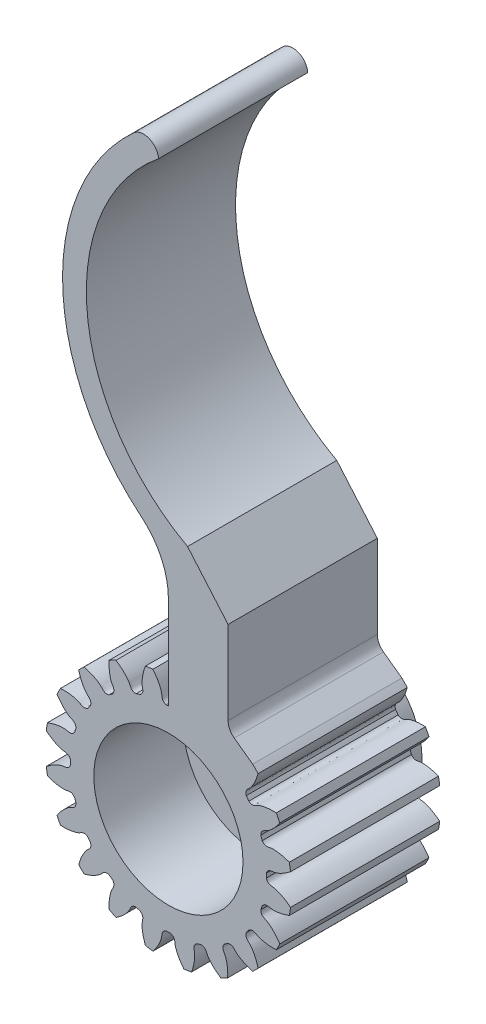
SolidWorks part; units mm, degrees
material "聚脂树脂"
ref_plane "前视基准面" through (0, 0, 0) normal (0, 0, 1) x (1, 0, 0)
ref_plane "上视基准面" through (0, 0, 0) normal (0, 1, 0) x (1, 0, 0)
ref_plane "右视基准面" through (0, 0, 0) normal (1, 0, 0) x (0, 0, -1)
other "Configuration Table"
sketch "草图1" plane through (0, 0, 0) normal (0, 0, 1) x (1, 0, 0)
  circle A0 centre (0, 0) radius 16.5
extrude "凸台-拉伸1" add sketch "草图1" along normal blind 20
ref_axis "基准轴1" through (0, 0, -1.5) along (0, 0, 1)
sketch "草图2" plane through (0, 0, 0) normal (0, 0, 1) x (1, 0, 0)
  line L0 (0, 0) -> (0, 16.5) construction
  circle A0 centre (0, 0) radius 16.5 construction
  arc A1 (0.29, 13.1218) -> (-0.29, 13.1218) centre (0, 0) ccw
  arc A2 (4.7717, 18.7474) -> (-4.7717, 18.7474) centre (0, 0) ccw
  spline S0 degree 3 poles (0.29, 13.1218) (0.9168, 13.3402) (0.8356, 13.7807) (0.9193, 14.205) (0.9283, 14.2463) (0.9395, 14.293) (0.9529, 14.3448) (0.969, 14.4018) (0.9878, 14.4638) (1.0095, 14.5309) (1.0345, 14.6028) (1.0629, 14.6795) (1.0948, 14.7608) (1.1305, 14.8467) (1.1702, 14.9371) (1.2141, 15.0317) (1.2623, 15.1305) (1.315, 15.2334) (1.3725, 15.3401) (1.4349, 15.4506) (1.5023, 15.5646) (1.575, 15.6821) (1.653, 15.8029) (1.7366, 15.9267) (1.826, 16.0534) (1.9211, 16.1829) (2.0223, 16.3149) (2.1296, 16.4493) (2.2432, 16.5859) (2.3632, 16.7244) (2.4897, 16.8646) (2.6229, 17.0065) (2.7628, 17.1496) (2.9095, 17.2939) (3.0632, 17.4391) (3.224, 17.585) (3.3918, 17.7313) (3.567, 17.8779) (3.7493, 18.0245) (3.9391, 18.1709) (4.1363, 18.3167) (4.4122, 18.5125) (4.6259, 18.6545) (4.7717, 18.7474) knots 0 0 0 0 0.165916 0.170906 0.176664 0.183189 0.190482 0.198542 0.207371 0.216967 0.22733 0.238462 0.250361 0.263027 0.276462 0.290664 0.305634 0.321371 0.337876 0.355149 0.37319 0.391998 0.411574 0.431917 0.453028 0.474907 0.497554 0.520968 0.54515 0.570099 0.595817 0.622302 0.649554 0.677575 0.706363 0.735918 0.766242 0.797333 0.829191 0.861818 0.895212 0.929373 1 1 1 1
  spline S1 degree 3 poles (-0.29, 13.1218) (-0.9168, 13.3402) (-0.8356, 13.7807) (-0.9193, 14.205) (-0.9283, 14.2463) (-0.9395, 14.293) (-0.9529, 14.3448) (-0.969, 14.4018) (-0.9878, 14.4638) (-1.0095, 14.5309) (-1.0345, 14.6028) (-1.0629, 14.6795) (-1.0948, 14.7608) (-1.1305, 14.8467) (-1.1702, 14.9371) (-1.2141, 15.0317) (-1.2623, 15.1305) (-1.315, 15.2334) (-1.3725, 15.3401) (-1.4349, 15.4506) (-1.5023, 15.5646) (-1.575, 15.6821) (-1.653, 15.8029) (-1.7366, 15.9267) (-1.826, 16.0534) (-1.9211, 16.1829) (-2.0223, 16.3149) (-2.1296, 16.4493) (-2.2432, 16.5859) (-2.3632, 16.7244) (-2.4897, 16.8646) (-2.6229, 17.0065) (-2.7628, 17.1496) (-2.9095, 17.2939) (-3.0632, 17.4391) (-3.224, 17.585) (-3.3918, 17.7313) (-3.567, 17.8779) (-3.7493, 18.0245) (-3.9391, 18.1709) (-4.1363, 18.3167) (-4.4122, 18.5125) (-4.6259, 18.6545) (-4.7717, 18.7474) knots 0 0 0 0 0.165916 0.170906 0.176664 0.183189 0.190482 0.198542 0.207371 0.216967 0.22733 0.238462 0.250361 0.263027 0.276462 0.290664 0.305634 0.321371 0.337876 0.355149 0.37319 0.391998 0.411574 0.431917 0.453028 0.474907 0.497554 0.520968 0.54515 0.570099 0.595817 0.622302 0.649554 0.677575 0.706363 0.735918 0.766242 0.797333 0.829191 0.861818 0.895212 0.929373 1 1 1 1
extrude "切除-拉伸1" cut sketch "草图2" along normal through all
pattern_circular "阵列(圆周)1" count 20 over 360 about axis through (0, 0, -1.5) along (0, 0, 1) of "切除-拉伸1"
sketch "草图3" plane through (0, 0, 0) normal (0, 0, 1) x (1, 0, 0)
  circle A0 centre (0, 0) radius 15 construction
  dimension "Dn" = 30
sketch "草图4" plane through (0, 0, 0) normal (0, 0, -1) x (-1, 0, 0)
  line L0 (0, 0) -> (67.6919, 0) construction
  line L1 (0, 13.125) -> (0, 76.7697) construction
  line L2 (-15, 0) -> (-15, 67.6903) construction
  line L6 (-7.9502, 14.4584) -> (-11.294, 12.029)
  line L7 (-8, 0) -> (-8, 30.72)
  line L8 (0, 30.72) -> (0, 0)
  line L9 (1.261, 80) -> (1.32, 76)
  line L10 (-8, 0) -> (0, 0)
  circle A2 centre (-15, 55.76) radius 26 construction
  arc A4 (-8, 30.72) -> (1.32, 76) centre (-15, 55.76) ccw
  arc A6 (0.29, 13.1218) -> (-0.29, 13.1218) centre (0, 0) ccw construction
  arc A7 (-2.0665, 16.3701) -> (-3.0932, 16.2075) centre (0, 0) ccw construction
  arc A8 (-3.7791, 12.5692) -> (-4.3306, 12.39) centre (0, 0) ccw construction
  arc A9 (-7.024, 14.9303) -> (-7.9502, 14.4584) centre (0, 0) ccw construction
  arc A10 (0, 13.125) -> (-0.29, 13.1218) centre (0, 0) ccw
  arc A11 (-2.0665, 16.3701) -> (-3.0932, 16.2075) centre (0, 0) ccw
  arc A12 (-3.7791, 12.5692) -> (-4.3306, 12.39) centre (0, 0) ccw
  arc A13 (-7.024, 14.9303) -> (-7.9502, 14.4584) centre (0, 0) ccw
  arc A14 (-7.4782, 10.7862) -> (-7.9474, 10.4453) centre (0, 0) ccw construction
  arc A15 (-7.4782, 10.7862) -> (-7.9474, 10.4453) centre (0, 0) ccw
  circle A16 centre (0, 0) radius 12.5
  circle A17 centre (-15, 55.76) radius 29.189 construction
  arc A18 (0, 30.72) -> (1.261, 80) centre (-15, 55.76) ccw
  spline S2 degree 3 poles (9636.1577, 2672.394) (-75.3968, -18.2301) (0.8601, 5.1856) (-0.9224, 14.2207) (-0.9359, 14.2793) (-0.9529, 14.3448) (-0.969, 14.4018) (-0.9951, 14.4881) (-1.0357, 14.6084) (-1.0961, 14.7664) (-1.1716, 14.9426) (-1.2638, 15.1361) (-1.3741, 15.3456) (-1.5041, 15.5702) (-1.6549, 15.8084) (-1.7965, 16.0133) (-1.9211, 16.1829) (-29.6649, 52.3852) (-347.1976, -138.1957) (9963.7292, 828.2221) knots -3.578314 -3.578314 -3.578314 -3.578314 0.165916 0.170906 0.183189 0.190482 0.198542 0.207371 0.22733 0.250361 0.276462 0.305634 0.337876 0.37319 0.411574 0.453028 0.474907 0.497554 19.082782 19.082782 19.082782 19.082782 only from (-0.29, 13.1218) to (-2.0665, 16.3701) construction
  spline S3 degree 3 poles (-9990.3457, -436.1387) (77.34, 5.961) (-2.4205, 4.666) (-3.5171, 13.8097) (-3.5224, 13.8696) (-3.5265, 13.9372) (-3.5289, 13.9963) (-3.5307, 14.0865) (-3.5293, 14.2134) (-3.5206, 14.3824) (-3.5033, 14.5733) (-3.4754, 14.7858) (-3.4352, 15.0192) (-3.381, 15.2729) (-3.3111, 15.5461) (-3.2398, 15.7847) (-3.1737, 15.9845) (12.0251, 58.9882) (372.9094, -24.1419) (-9732.0043, -2291.2756) knots -3.085746 -3.085746 -3.085746 -3.085746 0.658484 0.663474 0.675757 0.68305 0.691111 0.699939 0.719899 0.742929 0.76903 0.798202 0.830445 0.865758 0.904142 0.945597 0.967475 0.990122 19.575351 19.575351 19.575351 19.575351 only from (-3.7791, 12.5692) to (-3.0932, 16.2075) construction
  spline S4 degree 3 poles (8338.7154, 5519.3342) (-66.0732, -40.6368) (-0.7844, 5.1976) (-5.2717, 13.2396) (-5.3027, 13.2912) (-5.3391, 13.3482) (-5.3719, 13.3975) (-5.4235, 13.4715) (-5.4992, 13.5733) (-5.6055, 13.705) (-5.7318, 13.8492) (-5.8792, 14.0047) (-6.0489, 14.1699) (-6.2419, 14.3433) (-6.459, 14.5233) (-6.6569, 14.6744) (-6.8279, 14.7972) (-44.4009, 40.6543) (-287.4997, -238.7219) (9220.1348, 3866.6477) knots -3.578314 -3.578314 -3.578314 -3.578314 0.165916 0.170906 0.183189 0.190482 0.198542 0.207371 0.22733 0.250361 0.276462 0.305634 0.337876 0.37319 0.411574 0.453028 0.474907 0.497554 19.082782 19.082782 19.082782 19.082782 only from (-4.3306, 12.39) to (-7.024, 14.9303) construction
  spline S5 degree 3 poles (-0.29, 13.1218) (-0.9168, 13.3402) (-0.8356, 13.7807) (-0.9224, 14.2207) (-0.9359, 14.2793) (-0.9529, 14.3448) (-0.969, 14.4018) (-0.9951, 14.4881) (-1.0357, 14.6084) (-1.0961, 14.7664) (-1.1716, 14.9426) (-1.2638, 15.1361) (-1.3741, 15.3456) (-1.5041, 15.5702) (-1.6549, 15.8084) (-1.828, 16.0589) (-1.969, 16.2466) (-2.0515, 16.3512) (-2.0665, 16.3701) knots 0 0 0 0 0.165916 0.170906 0.183189 0.190482 0.198542 0.207371 0.22733 0.250361 0.276462 0.305634 0.337876 0.37319 0.411574 0.453028 0.497554 0.507432 0.507432 0.507432 0.507432
  spline S6 degree 3 poles (-3.7791, 12.5692) (-3.2504, 12.9706) (-3.4637, 13.3644) (-3.5171, 13.8097) (-3.5224, 13.8696) (-3.5265, 13.9372) (-3.5289, 13.9963) (-3.5307, 14.0865) (-3.5293, 14.2134) (-3.5206, 14.3824) (-3.5033, 14.5733) (-3.4754, 14.7858) (-3.4352, 15.0192) (-3.381, 15.2729) (-3.3111, 15.5461) (-3.224, 15.8378) (-3.1479, 16.0599) (-3.1017, 16.1848) (-3.0932, 16.2075) knots 0.492568 0.492568 0.492568 0.492568 0.658484 0.663474 0.675757 0.68305 0.691111 0.699939 0.719899 0.742929 0.76903 0.798202 0.830445 0.865758 0.904142 0.945597 0.990122 1 1 1 1
  spline S7 degree 3 poles (-4.3306, 12.39) (-4.9943, 12.404) (-5.0532, 12.848) (-5.2717, 13.2396) (-5.3027, 13.2912) (-5.3391, 13.3482) (-5.3719, 13.3975) (-5.4235, 13.4715) (-5.4992, 13.5733) (-5.6055, 13.705) (-5.7318, 13.8492) (-5.8792, 14.0047) (-6.0489, 14.1699) (-6.2419, 14.3433) (-6.459, 14.5233) (-6.701, 14.7081) (-6.8931, 14.843) (-7.0039, 14.9169) (-7.024, 14.9303) knots 0 0 0 0 0.165916 0.170906 0.183189 0.190482 0.198542 0.207371 0.22733 0.250361 0.276462 0.305634 0.337876 0.37319 0.411574 0.453028 0.497554 0.507432 0.507432 0.507432 0.507432
  spline S8 degree 3 poles (-9366.6091, -3501.9792) (71.7127, 29.5686) (-3.7439, 3.6897) (-7.6124, 12.047) (-7.636, 12.1023) (-7.6607, 12.1653) (-7.6812, 12.2208) (-7.7108, 12.3061) (-7.7487, 12.4272) (-7.7927, 12.5905) (-7.8352, 12.7775) (-7.8743, 12.9882) (-7.9082, 13.2226) (-7.9351, 13.4806) (-7.9531, 13.762) (-7.959, 14.011) (-7.9578, 14.2215) (-6.7918, 59.817) (362.1182, 92.275) (-8547.643, -5186.4873) knots -3.085746 -3.085746 -3.085746 -3.085746 0.658484 0.663474 0.675757 0.68305 0.691111 0.699939 0.719899 0.742929 0.76903 0.798202 0.830445 0.865758 0.904142 0.945597 0.967475 0.990122 19.575351 19.575351 19.575351 19.575351 only from (-7.4782, 10.7862) to (-7.9502, 14.4584) construction
  spline S9 degree 3 poles (6225.0215, 7826.0035) (-50.2819, -59.0656) (-2.3522, 4.7008) (-9.105, 10.9626) (-9.1503, 11.0021) (-9.2026, 11.0451) (-9.2491, 11.0817) (-9.321, 11.1362) (-9.4245, 11.2097) (-9.5662, 11.302) (-9.7309, 11.4002) (-9.9192, 11.5025) (-10.1316, 11.6072) (-10.3687, 11.7125) (-10.6308, 11.8165) (-10.8658, 11.8991) (-11.0663, 11.963) (-54.7906, 24.9439) (-199.6594, -315.8803) (7574.0095, 6526.5788) knots -3.578314 -3.578314 -3.578314 -3.578314 0.165916 0.170906 0.183189 0.190482 0.198542 0.207371 0.22733 0.250361 0.276462 0.305634 0.337876 0.37319 0.411574 0.453028 0.474907 0.497554 19.082782 19.082782 19.082782 19.082782 only from (-7.9474, 10.4453) to (-11.294, 12.029) construction
  spline S10 degree 3 poles (-7.4782, 10.7862) (-7.0995, 11.3313) (-7.424, 11.64) (-7.6124, 12.047) (-7.636, 12.1023) (-7.6607, 12.1653) (-7.6812, 12.2208) (-7.7108, 12.3061) (-7.7487, 12.4272) (-7.7927, 12.5905) (-7.8352, 12.7775) (-7.8743, 12.9882) (-7.9082, 13.2226) (-7.9351, 13.4806) (-7.9531, 13.762) (-7.9603, 14.0664) (-7.9566, 14.3011) (-7.9513, 14.4342) (-7.9502, 14.4584) knots 0.492568 0.492568 0.492568 0.492568 0.658484 0.663474 0.675757 0.68305 0.691111 0.699939 0.719899 0.742929 0.76903 0.798202 0.830445 0.865758 0.904142 0.945597 0.990122 1 1 1 1
  spline S11 degree 3 poles (-7.9474, 10.4453) (-8.5829, 10.2536) (-8.7761, 10.6576) (-9.105, 10.9626) (-9.1503, 11.0021) (-9.2026, 11.0451) (-9.2491, 11.0817) (-9.321, 11.1362) (-9.4245, 11.2097) (-9.5662, 11.302) (-9.7309, 11.4002) (-9.9192, 11.5025) (-10.1316, 11.6072) (-10.3687, 11.7125) (-10.6308, 11.8165) (-10.9181, 11.9175) (-11.1425, 11.9864) (-11.2707, 12.0225) (-11.294, 12.029) knots 0 0 0 0 0.165916 0.170906 0.183189 0.190482 0.198542 0.207371 0.22733 0.250361 0.276462 0.305634 0.337876 0.37319 0.411574 0.453028 0.497554 0.507432 0.507432 0.507432 0.507432
  dimension "D4" = 52
  dimension "D5" = 80
  dimension "D3" = 25
  dimension "D1" = 15
  dimension "D2" = 30.72
  dimension "D6" = 76
  dimension "D8" = 8
  dimension "D9" = 30.72
extrude "凸台-拉伸2" add sketch "草图4" against normal blind 20 contours S7 A12 S6 A11 S5 A10 L8 A18 L9 A4 L7 L6 A13 | S11 L7 L6 | L6 S11 A15 S10 region at (7.2884, 22.5711, 0) region at (9.051, 12.2758, 0)
fillet "圆角1" radius 10 1 edges at (0, 30.72, 10)
fillet "圆角2" radius 2 2 edges at (8, 14.4222, 10) (-1.261, 80, 10)
sketch "草图5" plane through (0, 0, 0) normal (0, 0, -1) x (-1, 0, 0)
  line L0 (0, 0) -> (47.9973, 0) construction
  line L1 (0, 0) -> (0, 54.3289) construction
sketch "草图7" plane through (0, 0, 20) normal (0, 0, 1) x (1, 0, 0)
  line L0 (0, 0) -> (42.9933, 0) construction
  line L1 (0, 0) -> (0, 51.6895) construction
  circle A0 centre (0, 0) radius 10
  dimension "D1" = 20
extrude "切除-拉伸2" cut sketch "草图7" against normal blind 12
sketch "草图8" plane through (0, 0, 8) normal (0, 0, 1) x (1, 0, 0)
  line L0 (0, 0) -> (25.4464, 0) construction
  line L1 (0, 0) -> (0, 31.9913) construction
  circle A0 centre (0, 0) radius 3.5
  circle A1 centre (0, 7) radius 1.5
  circle A2 centre (7, 0) radius 1.5
  circle A3 centre (0, -7) radius 1.5
  circle A4 centre (-7, 0) radius 1.5
  dimension "D1" = 3
  dimension "D2" = 7
  dimension "D4" = 3
  dimension "D3" = 7
  dimension "D5" = 7
extrude "切除-拉伸3" cut sketch "草图8" against normal blind 10
chamfer "倒角1" distance 5 angle 45 1 edges at (8, 30.72, 10) first distance on face at (8, 23.0806, 10)
sketch "草图10" plane through (0, 0, 0) normal (0, 0, -1) x (-1, 0, 0)
  circle A0 centre (0, 0) radius 10
  circle A1 centre (-7, 0) radius 1.5 construction
  circle A2 centre (0, -7) radius 1.5 construction
  circle A3 centre (0, 0) radius 3.5 construction
  circle A4 centre (7, 0) radius 1.5 construction
  circle A5 centre (0, 7) radius 1.5 construction
  circle A6 centre (-7, 0) radius 1.5
  circle A7 centre (0, -7) radius 1.5
  circle A8 centre (0, 0) radius 3.5
  circle A9 centre (7, 0) radius 1.5
  circle A10 centre (0, 7) radius 1.5
  dimension "D1" = 20
extrude "凸台-拉伸3" add sketch "草图10" along normal blind 4
fillet "圆角3" radius 2 1 edges at (10, 0, 0)
